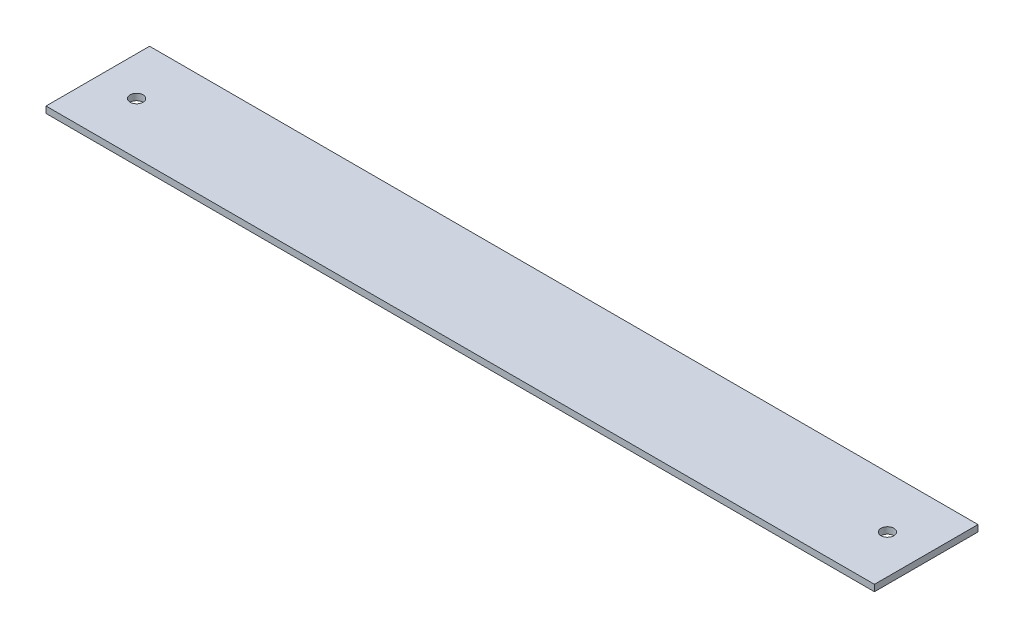
SolidWorks part; units mm, degrees
ref_plane "Front Plane" through (0, 0, 0) normal (0, 0, 1) x (1, 0, 0)
ref_plane "Top Plane" through (0, 0, 0) normal (0, 1, 0) x (1, 0, 0)
ref_plane "Right Plane" through (0, 0, 0) normal (1, 0, 0) x (0, 0, -1)
sketch "Sketch1" plane through (0, 0, 0) normal (0, 1, 0) x (1, 0, 0)
  line L1 (0, 0) -> (406.4, 0)
  line L2 (0, 0) -> (0, 50.8)
  line L3 (0, 50.8) -> (406.4, 50.8)
  line L4 (406.4, 0) -> (406.4, 50.8)
  dimension "D1" = 406.4
  dimension "D2" = 50.8
extrude "Boss-Extrude1" add sketch "Sketch1" along normal blind 3.175
sketch "Sketch2" plane through (0, 0, 0) normal (0, -1, 0) x (-1, 0, 0)
  line L0 (-406.4, 0) -> (-406.4, 50.8) construction
  line L1 (0, 0) -> (-406.4, 0) construction
  circle A0 centre (-387.35, 25.4) radius 3.175
  circle A1 centre (-19.05, 25.4) radius 3.175
  dimension "D1" = 19.05
  dimension "D2" = 25.4
  dimension "D3" = 25.4
  dimension "D4" = 387.35
extrude "Cut-Extrude1" cut sketch "Sketch2" against normal blind 24.638
